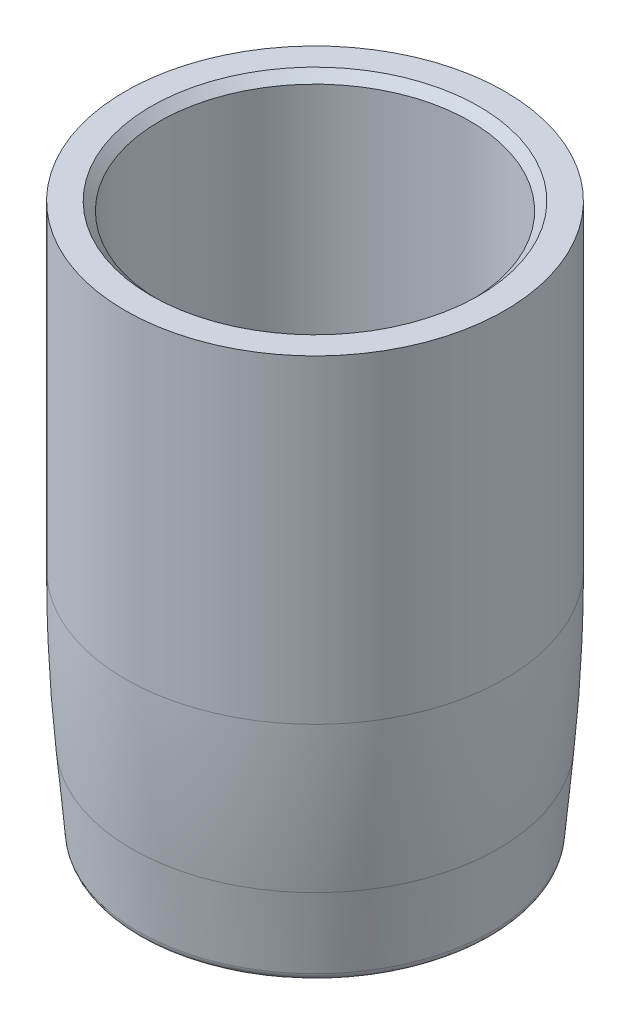
SolidWorks part; units mm, degrees
ref_plane "Front Plane" through (0, 0, 0) normal (0, 0, 1) x (1, 0, 0)
ref_plane "Top Plane" through (0, 0, 0) normal (0, 1, 0) x (1, 0, 0)
ref_plane "Right Plane" through (0, 0, 0) normal (1, 0, 0) x (0, 0, -1)
sketch "Sketch1" plane through (0, 0, 0) normal (0, 1, 0) x (1, 0, 0)
  circle A0 centre (0, 0) radius 5
  circle A1 centre (0, 0) radius 11
  dimension "D1" = 10
  dimension "D2" = 22
extrude "Boss-Extrude1" add sketch "Sketch1" along normal blind 2
sketch "Sketch2" plane through (0, 2, 0) normal (0, 1, 0) x (1, 0, 0)
  circle A0 centre (0, 0) radius 9
  circle A1 centre (0, 0) radius 11
  circle A2 centre (0, 0) radius 11 construction
  dimension "D1" = 18
extrude "Boss-Extrude2" add sketch "Sketch2" along normal blind 30
chamfer "Chamfer1" distance 0.8 angle 85 1 edges at (0, 0, 11) first distance on face at (0, 0, 11)
chamfer "Chamfer2" distance 0.5 angle 45 1 edges at (0, 32, 9)
fillet "Fillet1" radius 0.5 1 edges at (0, 0, 10.2)
fillet "Fillet2" radius 100 1 edges at (0, 9.144, 11)
chamfer "Chamfer3" distance 0.5 angle 45 1 edges at (0, 2, 5)
